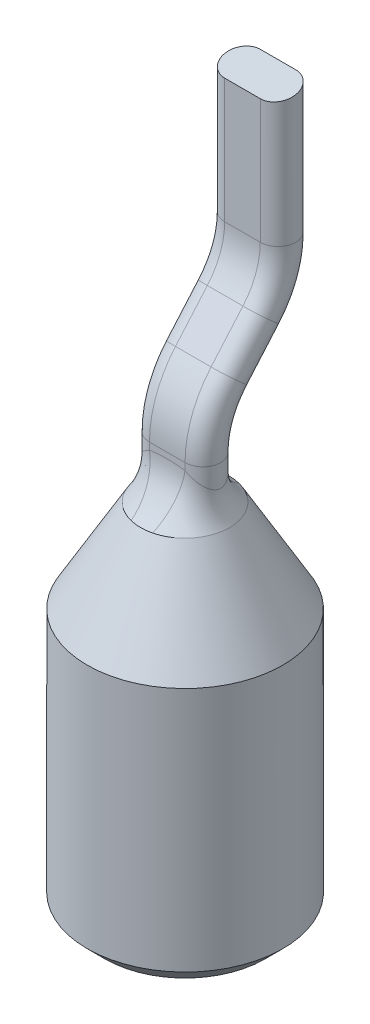
SolidWorks part; units mm, degrees
ref_plane "Front Plane" through (0, 0, 0) normal (0, 0, 1) x (1, 0, 0)
ref_plane "Top Plane" through (0, 0, 0) normal (0, 1, 0) x (1, 0, 0)
ref_plane "Right Plane" through (0, 0, 0) normal (1, 0, 0) x (0, 0, -1)
sketch "Sketch1" plane through (0, 0, 0) normal (0, 1, 0) x (1, 0, 0)
  circle A0 centre (0, 0) radius 5.5
  dimension "D1" = 11
extrude "Boss-Extrude1" add sketch "Sketch1" along normal blind 20
chamfer "Chamfer1" distance 3 angle 60 1 edges at (0, 20, 5.5) first distance on face at (0, 20, 5.5)
chamfer "Chamfer2" distance 1 angle 45 1 edges at (0, 0, 5.5)
sketch "Sketch2" plane through (0, 20, 0) normal (0, 1, 0) x (1, 0, 0)
  line L0 (-1, 0) -> (1, 0) construction
  line L1 (-1, 1) -> (1, 1)
  line L2 (-1, -1) -> (1, -1)
  arc A0 (-1, 1) -> (-1, -1) centre (-1, 0) ccw
  arc A1 (1, -1) -> (1, 1) centre (1, 0) ccw
  point P2 (0, 0)
  dimension "D1" = 1
  dimension "D2" = 2
sketch "Sketch3" plane through (0, 0, 0) normal (1, 0, 0) x (0, 0, -1)
  line L0 (0, 20) -> (0, 22.9143)
  line L1 (1, 20) -> (-1, 20) construction
  line L2 (1.2187, 26.1857) -> (3.0098, 28.2559)
  line L3 (4.2285, 31.5273) -> (4.2285, 58.8107)
  line L4 (-5.7715, 68.8107) -> (-10.1002, 68.8107)
  line L5 (-20.1002, 58.8107) -> (-20.1002, -28.4742)
  arc A0 (-10.1002, 68.8107) -> (-20.1002, 58.8107) centre (-10.1002, 58.8107) ccw
  arc A1 (4.2285, 58.8107) -> (-5.7715, 68.8107) centre (-5.7715, 58.8107) ccw
  arc A2 (4.2285, 31.5273) -> (3.0098, 28.2559) centre (-0.7715, 31.5273) cw
  arc A3 (1.2187, 26.1857) -> (0, 22.9143) centre (5, 22.9143) ccw
  dimension "D1" = 10
  dimension "D2" = 5
sweep "Sweep1" add profiles "Sketch2" path "Sketch3"
fillet "Fillet1" radius 3 1 edges at (0, 20, 1)
ref_plane "Plane1" through (0, 0, 20.1002) normal (0, 0, 1) x (1, 0, 0)
sketch "Sketch4" plane through (0, 0, 20.1002) normal (0, 0, 1) x (1, 0, 0)
  line L0 (1, -28.4742) -> (1, -33.3467)
  line L2 (11, -43.3467) -> (14.811, -43.3467)
  line L3 (24.811, -33.3467) -> (24.811, 1.1769)
  line L4 (34.811, 11.1769) -> (42.36, 11.1769)
  arc A0 (24.811, -33.3467) -> (14.811, -43.3467) centre (14.811, -33.3467) cw
  arc A1 (11, -43.3467) -> (1, -33.3467) centre (11, -33.3467) cw
  arc A2 (24.811, 1.1769) -> (34.811, 11.1769) centre (34.811, 1.1769) cw
  dimension "D1" = 10
  dimension "D2" = 10
sketch "Sketch5" plane through (0, 0, 20.1002) normal (0, 0, 1) x (1, 0, 0)
  line L0 (-1, -28.4742) -> (-1, -45.6927)
  line L1 (-2, -28.4742) -> (-1, -28.4742) construction
  line L2 (-1, 58.8107) -> (-1, -28.4742) construction
  line L3 (9, -55.6927) -> (55.3438, -55.6927)
  arc A0 (-1, -45.6927) -> (9, -55.6927) centre (9, -45.6927) ccw
  dimension "D1" = 10
  dimension "D3" = 56.3438
sketch "Sketch6" plane through (0, -28.4742, 0) normal (0, -1, 0) x (1, 0, 0)
  line L0 (11, 20.1002) -> (1, 20.1002) construction
  line L1 (9, 20.1002) -> (-1, 20.1002) construction
  circle A0 centre (1, 20.1002) radius 1
sketch "Sketch7" plane through (0, -28.4742, 0) normal (0, -1, 0) x (1, 0, 0)
  line L0 (9, 20.1002) -> (-1, 20.1002) construction
  line L1 (1.1, 20.1002) -> (-1.1, 20.1002) construction
  circle A0 centre (-1, 20.1002) radius 0.9837
sweep "Sweep2" add profiles "Sketch6" path "Sketch4"
sweep "Sweep4" add profiles "Sketch7" path "Sketch5"
ref_point "Point1"
ref_point "Point2"
ref_plane "Plane2" through (0, -55.6927, 0) normal (0, 1, 0) x (1, 0, 0)
ref_plane "Plane3" through (0, 11.1769, 0) normal (0, 1, 0) x (1, 0, 0)
sketch "Sketch9" plane through (42.36, 0, 0) normal (1, 0, 0) x (0, 0, -1)
  circle A1 centre (-20.1002, 11.1769) radius 1
  circle A2 centre (-20.1002, 11.1769) radius 1
  dimension "D1" = 0
sketch "Sketch10" plane through (55.3438, 0, 0) normal (1, 0, 0) x (0, 0, -1)
  circle A1 centre (-20.1002, -55.6927) radius 0.9837
  circle A2 centre (-20.1002, -55.6927) radius 0.9837
  dimension "D1" = 0
sketch "Sketch11" plane through (0, 11.1769, 0) normal (0, 1, 0) x (1, 0, 0)
  line L0 (42.36, -20.1002) -> (45.8216, -20.1002)
  line L1 (42.36, -21.1002) -> (42.36, -19.1002) construction
  line L2 (48.8216, -17.1002) -> (48.8216, -16.8521)
  arc A0 (48.8216, -17.1002) -> (45.8216, -20.1002) centre (45.8216, -17.1002) cw
  dimension "D1" = 3
sketch "Sketch12" plane through (0, -55.6927, 0) normal (0, 1, 0) x (1, 0, 0)
  line L0 (55.3438, -20.1002) -> (62.1442, -20.1002)
  line L1 (55.3438, -21.084) -> (55.3438, -19.1165) construction
  line L2 (65.1442, -23.1002) -> (65.1442, -44.2129)
  arc A0 (65.1442, -23.1002) -> (62.1442, -20.1002) centre (62.1442, -23.1002) ccw
  dimension "D1" = 3
sweep "Sweep5" add profiles "Sketch9" path "Sketch11"
sweep "Sweep6" add profiles "Sketch10" path "Sketch12"
sketch "Sketch13" plane through (0, 0, 0) normal (1, 0, 0) x (0, 0, -1)
  line L0 (-4.1755, 37.0178) -> (23.8782, 42.6996)
  line L1 (23.8782, 42.6996) -> (1.5063, 74.482)
  line L2 (1.5063, 74.482) -> (-56.5542, 64.5389)
  line L3 (-56.5542, 64.5389) -> (-74.3098, -56.1986)
  line L4 (-74.3098, -56.1986) -> (-10.0408, -65.6499)
  line L5 (-10.0408, -65.6499) -> (-4.5991, -28.6466)
  line L6 (-4.5991, -28.6466) -> (-11.8104, 28.1401)
  line L7 (-11.8104, 28.1401) -> (-4.1755, 37.0178)
extrude "Cut-Extrude1" cut sketch "Sketch13" against normal through all both and the other way through all
